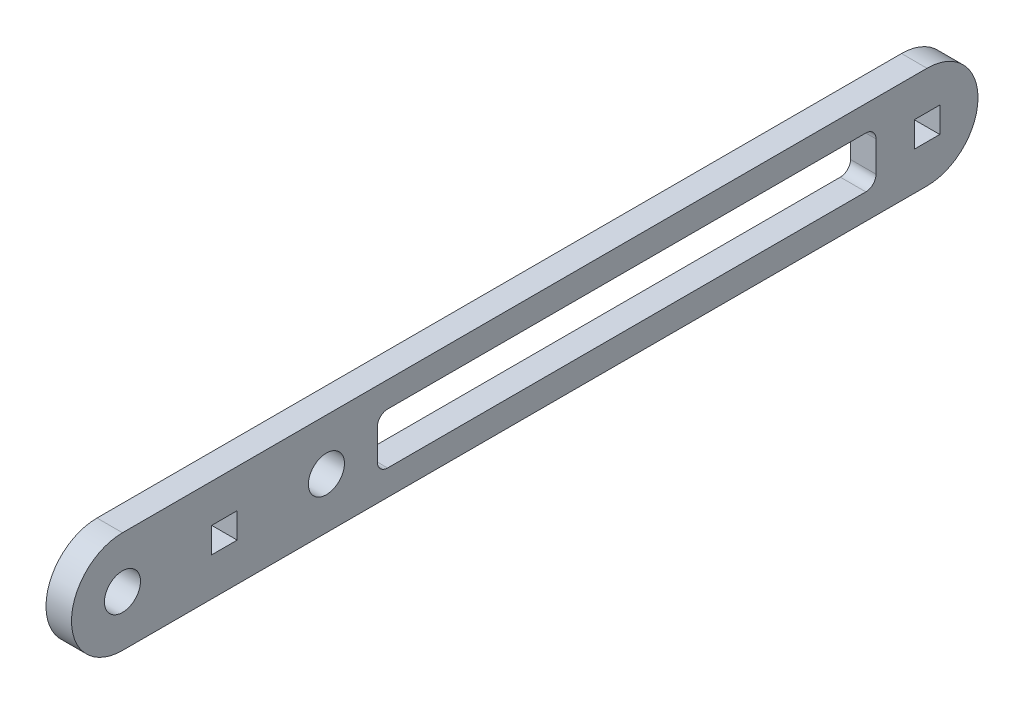
SolidWorks part; units mm, degrees
material "Custom Plastic"
ref_plane "Front Plane" through (0, 0, 0) normal (0, 0, 1) x (1, 0, 0)
ref_plane "Top Plane" through (0, 0, 0) normal (0, 1, 0) x (1, 0, 0)
ref_plane "Right Plane" through (0, 0, 0) normal (1, 0, 0) x (0, 0, -1)
sketch "Sketch1" plane through (0, 0, 0) normal (1, 0, 0) x (0, 0, -1)
  line L0 (0, 0) -> (-87.503, 0) construction
  line L1 (-101.7905, -1.5875) -> (-98.6155, 1.5875) construction
  line L2 (-85.9155, -1.5875) -> (-89.0905, -1.5875)
  line L3 (-85.9155, -1.5875) -> (-85.9155, 1.5875)
  line L4 (-85.9155, 1.5875) -> (-89.0905, 1.5875)
  line L5 (-89.0905, -1.5875) -> (-89.0905, 1.5875)
  line L6 (-85.9155, -1.5875) -> (-89.0905, 1.5875) construction
  line L7 (-85.9155, 1.5875) -> (-89.0905, -1.5875) construction
  line L8 (-76.3905, -1.5875) -> (-73.2155, 1.5875) construction
  line L9 (-100.203, 0) -> (-87.503, 0) construction
  line L10 (-100.203, 6.35) -> (0, 6.35)
  line L11 (-100.203, 6.35) -> (-100.203, 0) construction
  line L12 (0, -6.35) -> (-100.203, -6.35)
  line L13 (-100.203, 0) -> (-100.203, -6.35) construction
  line L14 (-68.453, 0) -> (-68.453, 1.905)
  line L15 (-67.183, 3.175) -> (-7.62, 3.175)
  line L16 (-6.35, 1.905) -> (-6.35, -1.905)
  line L17 (-7.62, -3.175) -> (-67.183, -3.175)
  line L18 (-68.453, -1.905) -> (-68.453, 0)
  line L20 (1.5875, -1.5875) -> (-1.5875, -1.5875)
  line L21 (1.5875, -1.5875) -> (1.5875, 1.5875)
  line L22 (1.5875, 1.5875) -> (-1.5875, 1.5875)
  line L23 (-1.5875, -1.5875) -> (-1.5875, 1.5875)
  line L24 (1.5875, -1.5875) -> (-1.5875, 1.5875) construction
  line L25 (1.5875, 1.5875) -> (-1.5875, -1.5875) construction
  circle A0 centre (-74.803, 0) radius 2.2451
  circle A1 centre (-100.203, 0) radius 2.2451
  circle A2 centre (0, 0) radius 2.2451 construction
  arc A3 (-100.203, 6.35) -> (-100.203, -6.35) centre (-100.203, 0) ccw
  arc A4 (0, 6.35) -> (0, -6.35) centre (0, 0) cw
  arc A5 (-7.62, 3.175) -> (-6.35, 1.905) centre (-7.62, 1.905) cw
  arc A6 (-6.35, -1.905) -> (-7.62, -3.175) centre (-7.62, -1.905) cw
  arc A7 (-67.183, -3.175) -> (-68.453, -1.905) centre (-67.183, -1.905) cw
  arc A8 (-68.453, 1.905) -> (-67.183, 3.175) centre (-67.183, 1.905) cw
  circle A9 centre (-87.503, 0) radius 2.2451 construction
  dimension "D5" = 6.35
  dimension "D9" = 1.27
  dimension "D1" = 87.503
  dimension "D2" = 3.175
  dimension "D3" = 12.7
  dimension "D4" = 12.7
  dimension "D6" = 6.35
  dimension "D7" = 6.35
  dimension "D8" = 3.175
extrude "Boss-Extrude1" add sketch "Sketch1" along normal blind 3.175
